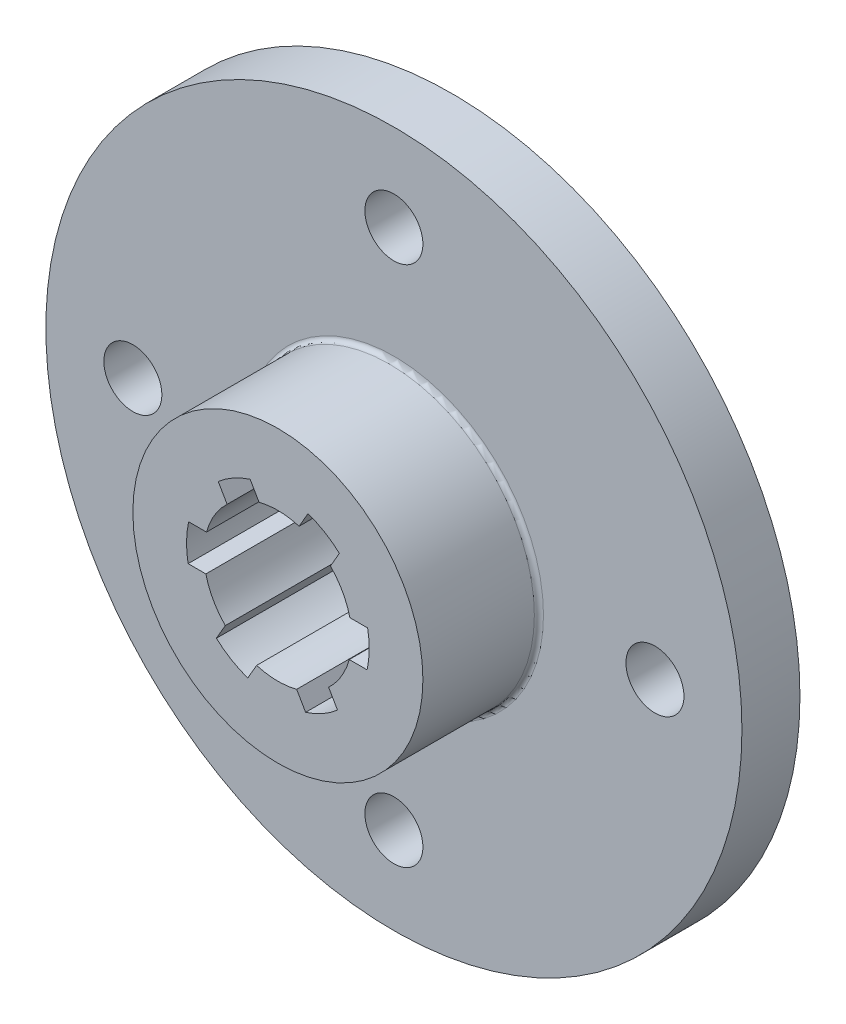
SolidWorks part; units mm, degrees
ref_plane "Front Plane" through (0, 0, 0) normal (0, 0, 1) x (1, 0, 0)
ref_plane "Top Plane" through (0, 0, 0) normal (0, 1, 0) x (1, 0, 0)
ref_plane "Right Plane" through (0, 0, 0) normal (1, 0, 0) x (0, 0, -1)
sketch "Sketch1" plane through (0, 0, 0) normal (0, 1, 0) x (1, 0, 0)
  line L0 (38.1, 3.175) -> (0, 3.175)
  line L1 (0, 3.175) -> (0, -3.175)
  line L2 (0, -3.175) -> (38.1, -3.175)
  line L3 (38.1, -3.175) -> (38.1, 3.175)
  line L4 (0, 3.175) -> (0, -3.175) construction
revolve "Revolve1" add sketch "Sketch1" angle 360 about L4 reverse direction yes
sketch "Sketch2" plane through (0, 0, 3.175) normal (0, 0, 1) x (1, 0, 0)
  circle A0 centre (0, 0) radius 15.875
extrude "Boss-Extrude1" add sketch "Sketch2" along normal blind 12.7
sketch "Sketch3" plane through (0, 0, 15.875) normal (0, 0, 1) x (1, 0, 0)
  line L0 (-7.8136, 2.1348) -> (-9.7695, 2.1348)
  line L1 (-9.8245, -1.8652) -> (-7.8823, -1.8652)
  line L2 (-5.7556, -5.6994) -> (-6.7336, -7.3932)
  line L3 (-3.297, -9.4409) -> (-2.3259, -7.7589)
  line L4 (2.058, -7.8342) -> (3.0359, -9.528)
  line L5 (6.5275, -7.5757) -> (5.5564, -5.8937)
  line L6 (7.8136, -2.1348) -> (9.7695, -2.1348)
  line L7 (9.8245, 1.8652) -> (7.8823, 1.8652)
  line L8 (5.7556, 5.6994) -> (6.7336, 7.3932)
  line L9 (3.297, 9.4409) -> (2.3259, 7.7589)
  line L10 (-2.058, 7.8342) -> (-3.0359, 9.528)
  line L11 (-6.5275, 7.5757) -> (-5.5564, 5.8937)
  arc A0 (-5.5564, 5.8937) -> (-7.8136, 2.1348) centre (0, 0) ccw
  arc A1 (-9.7695, 2.1348) -> (-9.8245, -1.8652) centre (0, 0) ccw
  arc A2 (-7.8823, -1.8652) -> (-5.7556, -5.6994) centre (0, 0) ccw
  arc A3 (-6.7336, -7.3932) -> (-3.297, -9.4409) centre (0, 0) ccw
  arc A4 (-2.3259, -7.7589) -> (2.058, -7.8342) centre (0, 0) ccw
  arc A5 (3.0359, -9.528) -> (6.5275, -7.5757) centre (0, 0) ccw
  arc A6 (5.5564, -5.8937) -> (7.8136, -2.1348) centre (0, 0) ccw
  arc A7 (9.7695, -2.1348) -> (9.8245, 1.8652) centre (0, 0) ccw
  arc A8 (7.8823, 1.8652) -> (5.7556, 5.6994) centre (0, 0) ccw
  arc A9 (6.7336, 7.3932) -> (3.297, 9.4409) centre (0, 0) ccw
  arc A10 (2.3259, 7.7589) -> (-2.058, 7.8342) centre (0, 0) ccw
  arc A11 (-3.0359, 9.528) -> (-6.5275, 7.5757) centre (0, 0) ccw
extrude "Cut-Extrude1" cut sketch "Sketch3" against normal blind 14.986
hole_wizard "Hole1" positions "Sketch7" profile "Sketch6" legacy end condition through all
sketch "Sketch7" plane through (0, 0, -3.175) normal (0, 0, -1) x (-1, 0, 0)
  point P0 (0, 28.575)
  point P1 (-28.575, 0)
  point P2 (28.575, 0)
  point P3 (0, -28.575)
sketch "Sketch6" plane through (0, 28.575, -3.175) normal (1, 0, 0) x (0, 1, 0)
  line L0 (0, 0) -> (0, 19.05)
  line L1 (0, 19.05) -> (3.175, 19.05)
  line L2 (3.175, 19.05) -> (3.175, 0)
  line L3 (3.175, 0) -> (0, 0)
  line L4 (0, 110) -> (0, -10) construction
  dimension "Diameter" = 6.35
  dimension "Depth" = 19.05
sketch "Sketch10" plane through (0, 0, 0.889) normal (0, 0, 1) x (1, 0, 0)
  circle A0 centre (0, 0) radius 4
  dimension "D1" = 8
extrude "Cut-Extrude3" cut sketch "Sketch10" against normal blind 10
fillet "Fillet2" radius 0.5 1 edges at (15.875, 0, 3.175)
